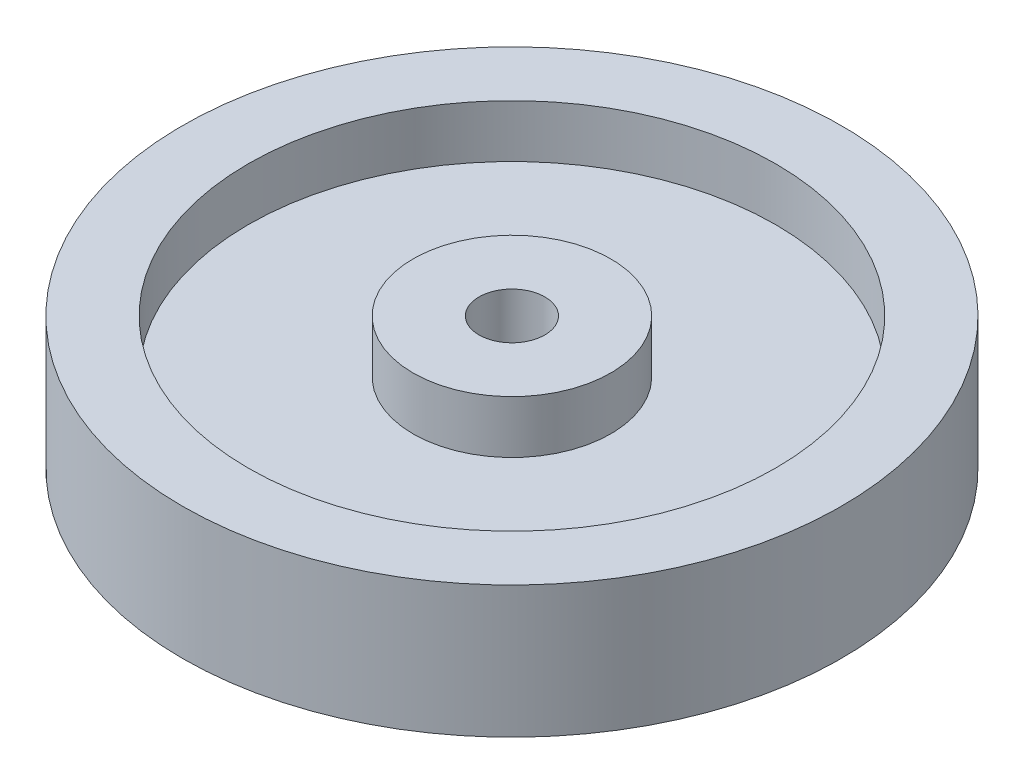
SolidWorks part; units mm, degrees
ref_plane "Front Plane" through (0, 0, 0) normal (0, 0, 1) x (1, 0, 0)
ref_plane "Top Plane" through (0, 0, 0) normal (0, 1, 0) x (1, 0, 0)
ref_plane "Right Plane" through (0, 0, 0) normal (1, 0, 0) x (0, 0, -1)
sketch "Sketch1" plane through (0, 0, 0) normal (0, 1, 0) x (1, 0, 0)
  circle A0 centre (0, 0) radius 7.5
  circle A1 centre (0, 0) radius 20
  circle A2 centre (0, 0) radius 25
  circle A3 centre (0, 0) radius 2.5
  dimension "D1" = 15
  dimension "D2" = 40
  dimension "D3" = 50
  dimension "D4" = 5
extrude "Boss-Extrude1" add sketch "Sketch1" along normal blind 5 and the other way blind 5 contours A0 | A2 A1 region at (-7.2879, 0, 0) region at (-24.2929, 0, 0)
extrude "Boss-Extrude2" add sketch "Sketch1<3>" along normal blind 1 and the other way blind 1 contours A1 A0 region at (-19.4343, 0, 0)
sketch "Sketch1<3>" plane through (0, 0, 0) normal (0, 1, 0) x (1, 0, 0) same geometry as "Sketch1"
